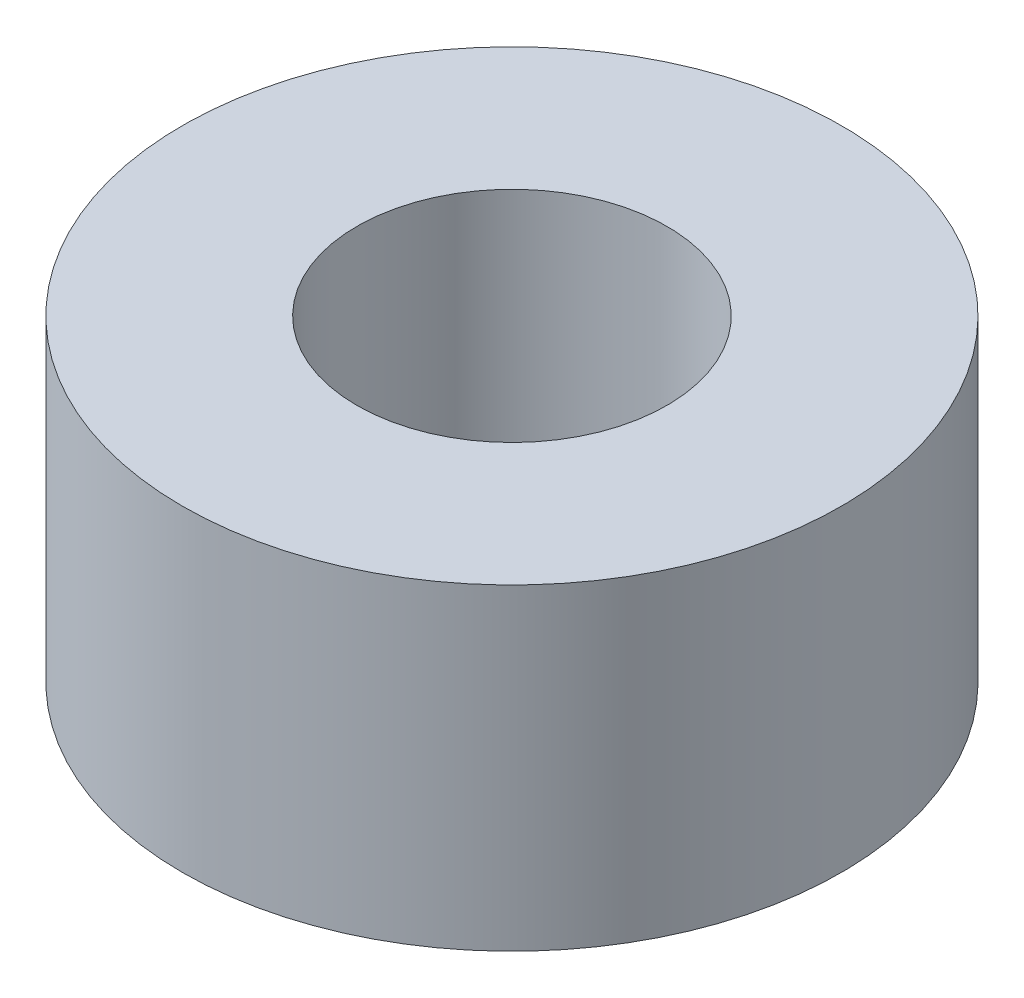
SolidWorks part; units mm, degrees
ref_plane "Front Plane" through (0, 0, 0) normal (0, 0, 1) x (1, 0, 0)
ref_plane "Top Plane" through (0, 0, 0) normal (0, 1, 0) x (1, 0, 0)
ref_plane "Right Plane" through (0, 0, 0) normal (1, 0, 0) x (0, 0, -1)
sketch "Sketch1" plane through (0, 0, 0) normal (0, 1, 0) x (1, 0, 0)
  circle A0 centre (0, 0) radius 2.2
  circle A1 centre (0, 0) radius 4.675
  dimension "D1" = 4.4
  dimension "D2" = 9.35
extrude "Boss-Extrude1" add sketch "Sketch1" along normal blind 4.5
